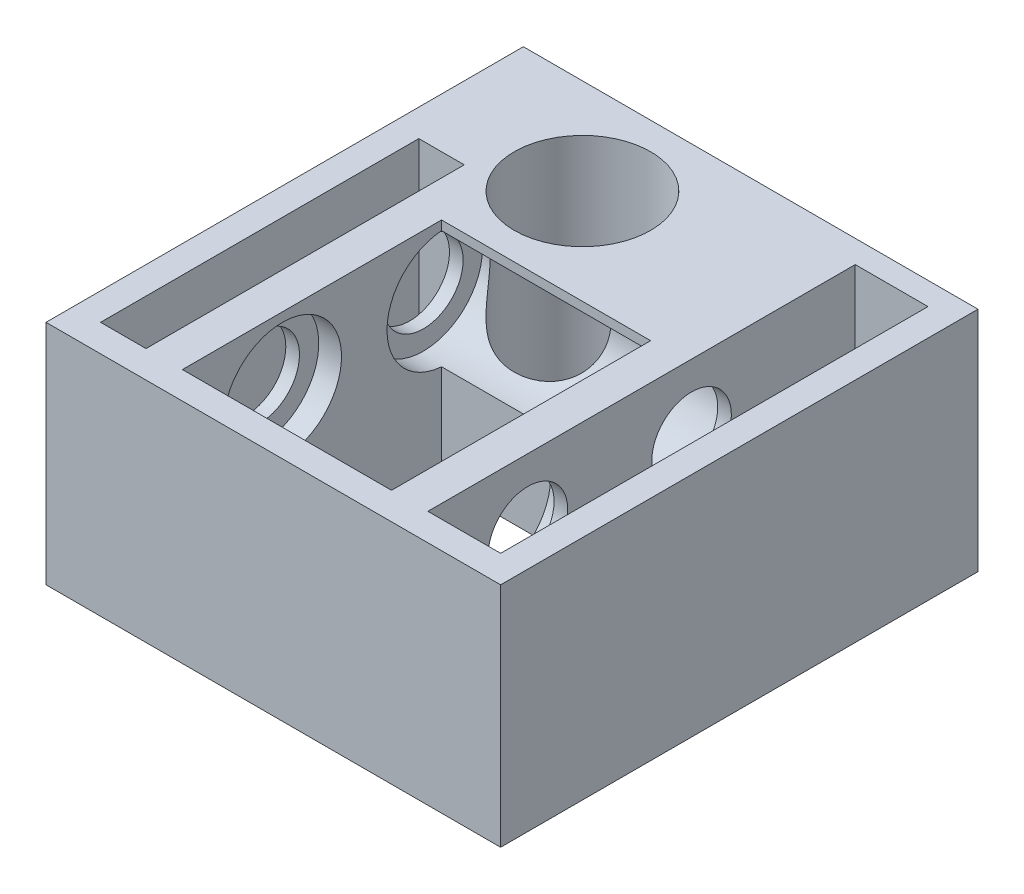
SolidWorks part; units mm, degrees
ref_plane "Front Plane" through (0, 0, 0) normal (0, 0, 1) x (1, 0, 0)
ref_plane "Top Plane" through (0, 0, 0) normal (0, 1, 0) x (1, 0, 0)
ref_plane "Right Plane" through (0, 0, 0) normal (1, 0, 0) x (0, 0, -1)
sketch "Sketch2" plane through (0, 0, 0) normal (0, 1, 0) x (1, 0, 0)
  line L0 (0, 54.9293) -> (0, -74.9036) construction
  line L1 (-50, 52.5) -> (50, 52.5)
  line L2 (-50, 52.5) -> (-50, -52.5)
  line L3 (-50, -52.5) -> (50, -52.5)
  line L4 (50, 52.5) -> (50, -52.5)
  line L5 (-72.7442, 0) -> (103.5154, 0) construction
  dimension "D1" = 105
  dimension "D2" = 100
extrude "Boss-Extrude1" add sketch "Sketch2" along normal blind 50
sketch "Sketch3" plane through (0, 50, 0) normal (0, 1, 0) x (1, 0, 0)
  line L0 (-69.2782, 0) -> (105.7343, 0) construction
  line L1 (0, 63.7563) -> (0, -72.2212) construction
  line L3 (-50, 52.5) -> (-50, -52.5) construction
  line L4 (50, 52.5) -> (-50, 52.5) construction
  circle A0 centre (-39, 0) radius 5 construction
  circle A1 centre (-39, 0) radius 39 construction
  circle A2 centre (-16.0054, 31.5) radius 15
  dimension "D1" = 10
  dimension "D2" = 6
  dimension "D3" = 78
  dimension "D4" = 30
  dimension "D5" = 6
extrude "Cut-Extrude1" cut sketch "Sketch3" against normal up to next
sketch "Sketch5" plane through (0, 50, 0) normal (0, 1, 0) x (1, 0, 0)
  line L0 (50, -52.5) -> (50, 52.5) construction
  line L1 (28, 33.5) -> (44, 33.5)
  line L2 (28, 33.5) -> (28, -46.5)
  line L3 (28, -46.5) -> (44, -46.5)
  line L4 (44, 33.5) -> (44, -46.5)
  line L5 (-44, 23.5) -> (-34, 23.5)
  line L6 (-44, 23.5) -> (-44, -46.5)
  line L7 (-44, -46.5) -> (-34, -46.5)
  line L8 (-34, 23.5) -> (-34, -46.5)
  line L9 (-50, -52.5) -> (50, -52.5) construction
  line L10 (-50, 52.5) -> (-50, -52.5) construction
  dimension "D1" = 6
  dimension "D2" = 6
  dimension "D3" = 80
  dimension "D4" = 16
  dimension "D5" = 6
  dimension "D6" = 6
  dimension "D7" = 70
  dimension "D8" = 10
extrude "Cut-Extrude3" cut sketch "Sketch5" against normal up to next
sketch "Sketch6" plane through (28, 0, 0) normal (1, 0, 0) x (0, 0, -1)
  line L0 (-6.5, 56.9811) -> (-6.5, -19.2113) construction
  line L1 (-69.1636, 35) -> (71.5534, 35) construction
  line L4 (-46.5, 0) -> (33.5, 0)
  line L5 (33.5, 0) -> (33.5, 50)
  line L6 (33.5, 50) -> (-46.5, 50)
  line L7 (-46.5, 50) -> (-46.5, 0)
  line L8 (-46.5, 0) -> (33.5, 0) construction
  line L9 (33.5, 0) -> (33.5, 50) construction
  line L10 (33.5, 50) -> (-46.5, 50) construction
  line L11 (-46.5, 50) -> (-46.5, 0) construction
  circle A0 centre (-24.5, 35) radius 13
  circle A2 centre (-24.5, 35) radius 9 construction
  circle A3 centre (11.5, 35) radius 13
  dimension "D4" = 26
  dimension "D5" = 18
  dimension "D2" = 40
  dimension "D3" = 35
  dimension "D6" = 18
  dimension "D7" = 18
  dimension "D1" = 0
extrude "Cut-Extrude4" cut sketch "Sketch6" against normal blind 31
sketch "Sketch7" plane through (28, 0, 0) normal (1, 0, 0) x (0, 0, -1)
  circle A0 centre (11.5, 35) radius 13 construction
  circle A1 centre (-24.5, 35) radius 13 construction
  circle A2 centre (11.5, 35) radius 13
  circle A3 centre (-24.5, 35) radius 13
  circle A4 centre (-24.5, 35) radius 8.75
  circle A5 centre (11.5, 35) radius 8.75
  dimension "D1" = 17.5
  dimension "D2" = 17.5
extrude "Boss-Extrude2" add sketch "Sketch7" against normal blind 3
ref_plane "Plane1" through (-3, 0, 0) normal (1, 0, 0) x (0, 0, -1)
mirror "Mirror1" about plane through (-3, 0, 0) normal (1, 0, 0) of "Boss-Extrude2", "Cut-Extrude4"
sketch "Sketch11" plane through (0, 50, 0) normal (0, 1, 0) x (1, 0, 0)
  line L0 (50, 52.5) -> (-50, 52.5) construction
  line L1 (28, 47.5) -> (44, 47.5)
  line L2 (28, 47.5) -> (28, 33.5)
  line L3 (28, 33.5) -> (44, 33.5)
  line L4 (44, 47.5) -> (44, 33.5)
  line L5 (44, -46.5) -> (44, 33.5) construction
  line L6 (28, 33.5) -> (28, -46.5) construction
  line L7 (44, 33.5) -> (28, 33.5) construction
  dimension "D1" = 5
extrude "Cut-Extrude7" cut sketch "Sketch11" against normal up to next
sketch "Sketch8" plane through (0, 50, 0) normal (0, 1, 0) x (1, 0, 0)
  line L0 (28, 47.5) -> (28, -46.5) construction
  line L1 (-26, 10.5) -> (20, 10.5)
  line L2 (-26, 10.5) -> (-26, -46.5)
  line L3 (-26, -46.5) -> (20, -46.5)
  line L4 (20, 10.5) -> (20, -46.5)
  line L5 (-34, -46.5) -> (-34, 23.5) construction
  line L6 (-50, -52.5) -> (50, -52.5) construction
  circle A0 centre (-16.0054, 31.5) radius 15 construction
  dimension "D4" = 6
  dimension "D1" = 8
  dimension "D2" = 8
  dimension "D3" = 6
extrude "Cut-Extrude5" cut sketch "Sketch8" against normal up to next
sketch "Sketch9" plane through (28, 0, 0) normal (1, 0, 0) x (0, 0, -1)
  line L2 (52.5, 50) -> (52.5, 0) construction
  line L4 (-52.5, 0) -> (52.5, 0) construction
  line L5 (-46.5, 0) -> (47.5, 0)
  line L6 (47.5, 0) -> (47.5, 50)
  line L7 (47.5, 50) -> (-46.5, 50)
  line L12 (-46.5, 50) -> (-46.5, 0)
  line L13 (-46.5, 0) -> (47.5, 0) construction
  line L15 (47.5, 50) -> (-46.5, 50) construction
  line L16 (-46.5, 50) -> (-46.5, 0) construction
  line L17 (35.5, 55.7455) -> (35.5, -7.8914) construction
  line L21 (47.5, 0) -> (47.5, 50) construction
  circle A7 centre (11.5, 35) radius 8.75 construction
  circle A8 centre (-24.5, 35) radius 8.75 construction
  circle A9 centre (11.5, 35) radius 8.75 construction
  circle A10 centre (-24.5, 35) radius 8.75 construction
  circle A11 centre (-24.5, 35) radius 18 construction
  circle A12 centre (11.5, 35) radius 18 construction
  circle A13 centre (35.5, 17) radius 12 construction
  circle A14 centre (35.5, 17) radius 1.6
  dimension "D2" = 36
  dimension "D3" = 36
  dimension "D4" = 24
  dimension "D5" = 5
  dimension "D6" = 5
  dimension "D7" = 3.2
  dimension "D8" = 17
  dimension "D1" = 0
sketch "Sketch10" plane through (0, 0, 0) normal (0, -1, 0) x (1, 0, 0)
  line L0 (28, -47.5) -> (28, -23.5) construction
  line L1 (5, -29.5) -> (25, -29.5)
  line L2 (5, -29.5) -> (5, -47.5)
  line L3 (5, -47.5) -> (25, -47.5)
  line L4 (25, -29.5) -> (25, -47.5)
  line L5 (-53.7581, -35.5) -> (88.6921, -35.5) construction
  line L7 (50, -52.5) -> (-50, -52.5) construction
  dimension "D1" = 20
  dimension "D2" = 3
  dimension "D3" = 18
  dimension "D4" = 17
  dimension "D5" = 6
  dimension "D6" = 5
extrude "Cut-Extrude8" cut sketch "Sketch9" against normal blind 3
extrude "Cut-Extrude9" cut sketch "Sketch10" against normal blind 22
